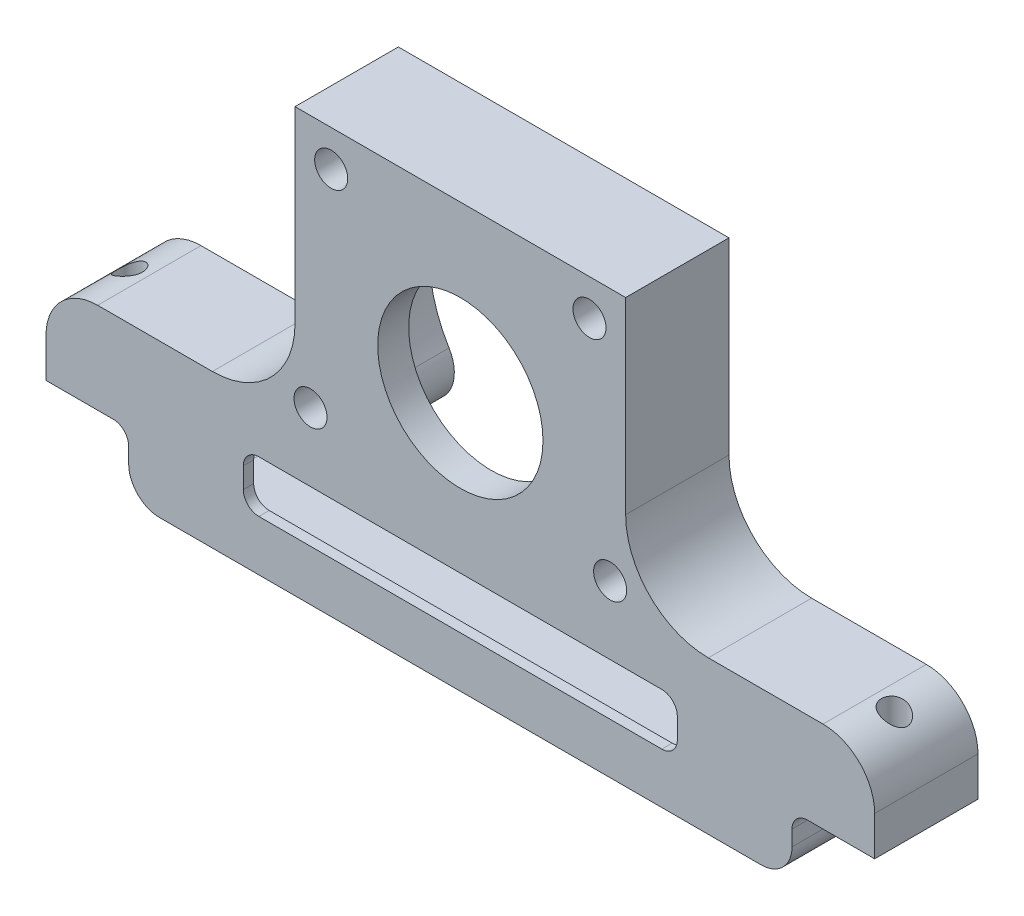
SolidWorks part; units mm, degrees
material "1060 Alloy"
ref_plane "Front Plane" through (0, 0, 0) normal (0, 0, 1) x (1, 0, 0)
ref_plane "Top Plane" through (0, 0, 0) normal (0, 1, 0) x (1, 0, 0)
ref_plane "Right Plane" through (0, 0, 0) normal (1, 0, 0) x (0, 0, -1)
sketch "Sketch1" plane through (0, 0, 0) normal (0, 0, 1) x (1, 0, 0)
  line L0 (-16, 38) -> (16, 38)
  line L1 (-20.1, 6.5) -> (20.1, 6.5) construction
  line L2 (-20.1, 6.5) -> (-20.1, 2.3) construction
  line L3 (-20.1, 2.3) -> (20.1, 2.3) construction
  line L4 (20.1, 6.5) -> (20.1, 2.3) construction
  line L5 (-20.1, 6.5) -> (20.1, 2.3) construction
  line L6 (-20.1, 2.3) -> (20.1, 6.5) construction
  line L7 (-26.1, 7) -> (26.1, 7) construction
  line L8 (-26.1, 7) -> (-26.1, 1.8) construction
  line L9 (-26.1, 1.8) -> (26.1, 1.8) construction
  line L10 (26.1, 7) -> (26.1, 1.8) construction
  line L11 (-26.1, 7) -> (26.1, 1.8) construction
  line L12 (-26.1, 1.8) -> (26.1, 7) construction
  line L13 (29.1, 9.8) -> (-29.1, 9.8) construction
  line L14 (29.1, 9.8) -> (29.1, -1) construction
  line L15 (29.1, -1) -> (-29.1, -1) construction
  line L16 (-29.1, 9.8) -> (-29.1, -1) construction
  line L17 (29.1, 9.8) -> (-29.1, -1) construction
  line L18 (29.1, -1) -> (-29.1, 9.8) construction
  line L19 (32.1, 11.8) -> (-32.1, 11.8) construction
  line L20 (32.1, 11.8) -> (32.1, -3) construction
  line L21 (32.1, -3) -> (-32.1, -3) construction
  line L22 (-32.1, 11.8) -> (-32.1, -3) construction
  line L23 (32.1, 11.8) -> (-32.1, -3) construction
  line L24 (32.1, -3) -> (-32.1, 11.8) construction
  line L25 (16, 38) -> (16, 11.8)
  line L26 (-16, 38) -> (-16, 11.8)
  line L27 (-16, 11.8) -> (-40.1, 11.8)
  line L28 (-40.1, 11.8) -> (-40.1, 3)
  line L29 (-40.1, 3) -> (-32.1, 3)
  line L30 (-32.1, 3) -> (-32.1, -3)
  line L31 (-32.1, -3) -> (32.1, -3)
  line L32 (32.1, -3) -> (32.1, 3)
  line L33 (32.1, 3) -> (40.1, 3)
  line L34 (40.1, 3) -> (40.1, 11.8)
  line L35 (40.1, 11.8) -> (16, 11.8)
  line L37 (-21, 6.9) -> (21, 6.9)
  line L38 (-21, 6.9) -> (-21, 1.9)
  line L39 (-21, 1.9) -> (21, 1.9)
  line L40 (21, 6.9) -> (21, 1.9)
  line L41 (-21, 6.9) -> (21, 1.9) construction
  line L42 (-21, 1.9) -> (21, 6.9) construction
  circle A0 centre (0, 22) radius 8
  circle A1 centre (0, 22) radius 13 construction
  point P2 (0, 4.4)
  point P5 (0, 4.4)
  point P13 (0, 4.4)
  point P18 (0, 4.4)
  point P34 (0, 4.4)
  dimension "D1" = 16
  dimension "D11" = 26
  dimension "D2" = 40.2
  dimension "D3" = 4.2
  dimension "D4" = 6
  dimension "D5" = 0.5
  dimension "D6" = 3
  dimension "D7" = 2.8
  dimension "D8" = 3
  dimension "D9" = 2
  dimension "D10" = 3
  dimension "D12" = 22
  dimension "D13" = 16
  dimension "D14" = 32
  dimension "D15" = 16
  dimension "D16" = 8
  dimension "D17" = 42
  dimension "D18" = 5
  dimension "D19" = 6
extrude "Boss-Extrude1" add sketch "Sketch1" along normal blind 10
fillet "Fillet1" radius 1.5 4 edges at (-21, 1.9, 5) (21, 1.9, 5) (21, 6.9, 5) (-21, 6.9, 5)
sketch "Sketch2" plane through (0, 0, 0) normal (0, 0, 1) x (1, 0, 0)
  circle A0 centre (0, 22) radius 13
  dimension "D1" = 26
extrude "Cut-Extrude1" cut sketch "Sketch2" along normal offset from surface (7 mm away) 3 up to face at (8, 22, 10)
sketch "Sketch3" plane through (0, 0, 0) normal (0, 0, 1) x (1, 0, 0)
  line L1 (-29.1, 9.9) -> (29.1, 9.9)
  line L2 (-29.1, 9.9) -> (-29.1, -1.1)
  line L3 (-29.1, -1.1) -> (29.1, -1.1)
  line L4 (29.1, 9.9) -> (29.1, -1.1)
  line L5 (-29.1, 9.9) -> (29.1, -1.1) construction
  line L6 (-29.1, -1.1) -> (29.1, 9.9) construction
  line L7 (0, 6.9) -> (0, 1.9) construction
  line L8 (19.5, 6.9) -> (-19.5, 6.9) construction
  line L9 (-19.5, 1.9) -> (19.5, 1.9) construction
  line L10 (-21, 4.4) -> (21, 4.4) construction
  line L11 (-21, 5.4) -> (-21, 3.4) construction
  line L12 (21, 3.4) -> (21, 5.4) construction
  line L14 (-20.1, 6.5) -> (20.1, 6.5) construction
  line L15 (-20.1, 6.5) -> (-20.1, 2.3) construction
  line L16 (-20.1, 2.3) -> (20.1, 2.3) construction
  line L17 (20.1, 6.5) -> (20.1, 2.3) construction
  line L18 (-20.1, 6.5) -> (20.1, 2.3) construction
  line L19 (-20.1, 2.3) -> (20.1, 6.5) construction
  point P0 (0, 4.4)
  point P17 (0, 4.4)
  dimension "D1" = 4.2
  dimension "D2" = 40.2
  dimension "D3" = 9
  dimension "D4" = 3.4
extrude "Cut-Extrude3" cut sketch "Sketch3" along normal offset from surface (9 mm away) 1 up to face at (8, 22, 10)
fillet "Fillet5" radius 8 2 edges at (-16, 11.8, 5) (16, 11.8, 5)
sketch "Sketch5" plane through (0, 0, 0) normal (0, 0, -1) x (-1, 0, 0)
  line L0 (-16, 38) -> (16, 38) construction
  line L1 (-16, 19.8) -> (-16, 38) construction
  line L2 (16, 38) -> (16, 19.8) construction
  circle A0 centre (-12.5, 34.5) radius 1.6
  circle A1 centre (12.5, 34.5) radius 1.6
  circle A2 centre (-14.5, 13.5) radius 1.6
  circle A3 centre (14.5, 13.5) radius 1.6
  dimension "D1" = 3.2
  dimension "D5" = 24.5
  dimension "D2" = 3.5
  dimension "D3" = 3.5
  dimension "D4" = 3.5
  dimension "D6" = 1.5
  dimension "D7" = 1.5
extrude "Cut-Extrude7" cut sketch "Sketch5" against normal up to next
fillet "Fillet4" radius 1.5 2 edges at (-32.1, 3, 5) (32.1, 3, 5)
fillet "Fillet6" radius 5 2 edges at (-40.1, 11.8, 5) (40.1, 11.8, 5)
hole_wizard "Tap Drill for M3 Tap1" positions "Sketch9" profile "Sketch8" hole size "M3" standard "ISO"
sketch "Sketch9" plane through (0, 3, 0) normal (0, -1, 0) x (-1, 0, 0)
  line L0 (-33.6, -10) -> (-40.1, -10) construction
  point P0 (-37, -5)
  point P2 (37, -5)
  dimension "D1" = 5
  dimension "D2" = 37
  dimension "D3" = 37
sketch "Sketch8" plane through (37, 3, 5) normal (1, 0, 0) x (0, 0, -1)
  line L0 (0, 0) -> (0, 13.7511)
  line L1 (0, 13.7511) -> (1.25, 13)
  line L2 (1.25, 13) -> (1.25, 0)
  line L5 (1.25, 0) -> (0, 0)
  line L10 (0, 13.7511) -> (-1.25, 13) construction
  line L11 (0, -6.35) -> (0, 107.95) construction
  dimension "Hole Dia." = 2.5
  dimension "Hole Depth" = 13
  dimension "Drill Angle" = 118
fillet "Fillet7" radius 3.5 2 edges at (-4.7529, 9.9, 3.5) (4.7529, 9.9, 3.5)
fillet "Fillet8" radius 1.5 4 edges at (29.1, -1.1, 4.5) (-29.1, -1.1, 4.5) (-29.1, 9.9, 4.5) (29.1, 9.9, 4.5)
fillet "Fillet9" radius 3 2 edges at (-32.1, -3, 5) (32.1, -3, 5)
